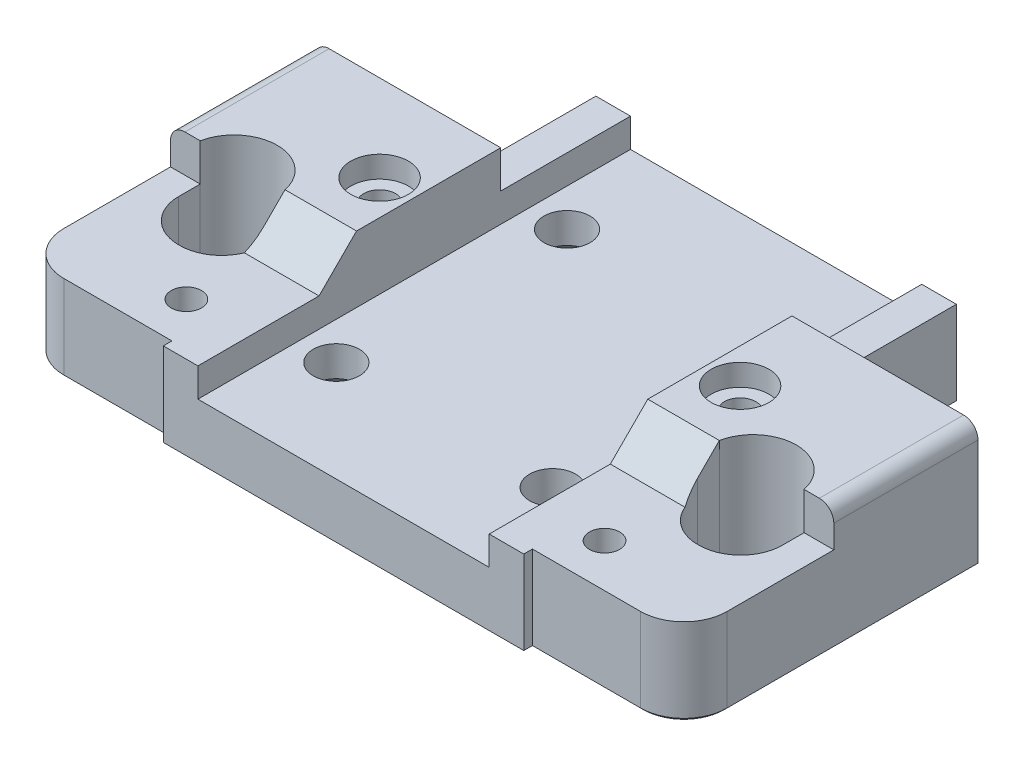
SolidWorks part; units mm, degrees
ref_plane "前视基准面" through (0, 0, 0) normal (0, 0, 1) x (1, 0, 0)
ref_plane "上视基准面" through (0, 0, 0) normal (0, 1, 0) x (1, 0, 0)
ref_plane "右视基准面" through (0, 0, 0) normal (1, 0, 0) x (0, 0, -1)
other "Configuration Table"
sketch "草图1" plane through (0, 0, 0) normal (0, 1, 0) x (1, 0, 0)
  line L1 (0, 0) -> (25, 0)
  line L2 (0, 0) -> (0, 30)
  line L3 (0, 30) -> (25, 30)
  line L4 (25, 0) -> (25, 30)
  circle A0 centre (5, 23) radius 1.6
  circle A1 centre (20, 23) radius 1.6
  circle A2 centre (20, 7) radius 1.6
  circle A3 centre (5, 7) radius 1.6
  dimension "D3" = 3.2
  dimension "D1" = 25
  dimension "D2" = 30
  dimension "D6" = 5
  dimension "D7" = 7
  dimension "D4" = 2
  dimension "D5" = 2
extrude "凸台-拉伸1" add sketch "草图1" along normal blind 4
sketch "草图5" plane through (0, 4, 0) normal (0, 1, 0) x (1, 0, 0)
  line L0 (0, 0) -> (25, 0) construction
  line L1 (0, 30) -> (2.4, 30)
  line L2 (0, 30) -> (0, 0)
  line L3 (0, 0) -> (2.4, 0)
  line L4 (2.4, 30) -> (2.4, 0)
  line L6 (25, 30) -> (22.6, 30)
  line L7 (25, 30) -> (25, 0)
  line L8 (25, 0) -> (22.6, 0)
  line L9 (22.6, 30) -> (22.6, 0)
  dimension "D1" = 2.4
  dimension "D2" = 2.4
extrude "凸台-拉伸4" add sketch "草图5" along normal blind 2
sketch "草图3" plane through (0, 0, 0) normal (0, -1, 0) x (-1, 0, 0)
  line L0 (0, 30) -> (0, 0) construction
  line L1 (0, 21) -> (10.5, 21)
  line L2 (0, 21) -> (0, 11)
  line L3 (0, 11) -> (10.5, 11)
  line L4 (10.5, 21) -> (10.5, 11)
  circle A0 centre (-5, 23) radius 1.6 construction
  dimension "D1" = 2
  dimension "D2" = 10.5
  dimension "D3" = 10
extrude "凸台-拉伸3" add sketch "草图3" against normal blind 8.6
sketch "草图4" plane through (0, 0, -21) normal (0, 0, -1) x (-1, 0, 0)
  line L1 (10.5, 8.6) -> (10.5, 0) construction
  line L2 (10.5, 8.6) -> (0, 8.6) construction
  circle A0 centre (5.5, 4.8) radius 3.15
  dimension "D1" = 6.3
  dimension "D2" = 3.8
  dimension "D3" = 5
extrude "切除-拉伸1" cut sketch "草图4" against normal blind 2.8
sketch "草图6" plane through (0, 0, 0) normal (0, -1, 0) x (-1, 0, 0)
  line L0 (0, 11) -> (10.5, 11) construction
  line L1 (10.5, 11) -> (10.5, 21) construction
  circle A0 centre (5.5, 10.4) radius 3
  dimension "D3" = 6
  dimension "D1" = 0.6
  dimension "D2" = 5
extrude "切除-拉伸2" cut sketch "草图6" against normal through all
ref_plane "基准面1" through (12.5, 0, 0) normal (1, 0, 0) x (0, 0, -1)
mirror "镜向1" about plane through (12.5, 0, 0) normal (1, 0, 0) of "凸台-拉伸3", "切除-拉伸1", "切除-拉伸2"
sketch "草图11" plane through (0, 0, 0) normal (0, -1, 0) x (-1, 0, 0)
  line L0 (-25, 30) -> (0, 30) construction
  line L2 (-23.1525, 15) -> (-24.0762, 16.6)
  line L3 (-24.0762, 16.6) -> (-25.9238, 16.6)
  line L4 (-25.9238, 16.6) -> (-26.8475, 15)
  line L5 (-26.8475, 15) -> (-25.9238, 13.4)
  line L6 (-25.9238, 13.4) -> (-24.0762, 13.4)
  line L7 (-24.0762, 13.4) -> (-23.1525, 15)
  line L8 (0.9238, 13.4) -> (1.8475, 15)
  line L9 (1.8475, 15) -> (0.9238, 16.6)
  line L10 (0.9238, 16.6) -> (-0.9238, 16.6)
  line L11 (-0.9238, 16.6) -> (-1.8475, 15)
  line L12 (-1.8475, 15) -> (-0.9238, 13.4)
  line L13 (-0.9238, 13.4) -> (0.9238, 13.4)
  circle A2 centre (-25, 15) radius 1.6 construction
  circle A3 centre (0, 15) radius 1.6 construction
  point P1 (-12.5, 30)
  dimension "D1" = 12.5
  dimension "D2" = 12.5
  dimension "D3" = 15
  dimension "D4" = 15
  dimension "D5" = 3.2
  dimension "D6" = 3.2
extrude "切除-拉伸3" cut sketch "草图11" against normal blind 4
sketch "草图18" plane through (0, 6, 0) normal (0, 1, 0) x (1, 0, 0)
  line L0 (22.6, 30) -> (22.6, 0) construction
  line L1 (25, 21) -> (22.6, 21)
  line L2 (25, 21) -> (25, 11)
  line L3 (25, 11) -> (22.6, 11)
  line L4 (22.6, 21) -> (22.6, 11)
  line L5 (2.4, 0) -> (2.4, 30) construction
  line L6 (0, 21) -> (2.4, 21)
  line L7 (0, 21) -> (0, 11)
  line L8 (0, 11) -> (2.4, 11)
  line L9 (2.4, 21) -> (2.4, 11)
extrude "凸台-拉伸8" add sketch "草图18" along normal up to surface (2.6 mm away) up to face at (-5.3333, 8.6, -14.7333)
sketch "草图12" plane through (0, 4, 0) normal (0, -1, 0) x (-1, 0, 0)
  circle A0 centre (0, 15) radius 1.1
  circle A1 centre (-25, 15) radius 1.1
  dimension "D1" = 2.2
  dimension "D2" = 2.2
extrude "切除-拉伸4" cut sketch "草图12" against normal through all
sketch "草图13" plane through (0, 8.6, 0) normal (0, 1, 0) x (1, 0, 0)
  circle A0 centre (0, 15) radius 2
  circle A1 centre (25, 15) radius 2
  dimension "D1" = 4
  dimension "D2" = 4
extrude "切除-拉伸5" cut sketch "草图13" against normal blind 1.5
chamfer "倒角10" distance 0.6 angle 45 2 edges at (0, 4, -16.1) (25, 4, -16.1)
sketch "草图22" plane through (0, 0, 0) normal (0, -1, 0) x (-1, 0, 0)
  line L0 (0, 0) -> (-25, 0) construction
  line L1 (0, 0.6) -> (10.5, 0.6)
  line L2 (0, 0.6) -> (0, 6.6)
  line L3 (0, 6.6) -> (8.4394, 6.6)
  line L4 (10.5, 0.6) -> (10.5, 6.6)
  line L5 (-25, 0.6) -> (-35.5, 0.6)
  line L6 (-25, 0.6) -> (-25, 6.6)
  line L7 (-25, 6.6) -> (-33.4394, 6.6)
  line L8 (-35.5, 0.6) -> (-35.5, 6.6)
  line L9 (-25, 0) -> (-25, 11) construction
  line L10 (0, 11) -> (0, 0) construction
  line L12 (-33.4394, 11) -> (-35.5, 11)
  line L13 (-33.4394, 11) -> (-33.4394, 6.6)
  line L15 (-35.5, 11) -> (-35.5, 6.6)
  line L16 (8.4394, 11) -> (10.5, 11)
  line L17 (8.4394, 11) -> (8.4394, 6.6)
  line L19 (10.5, 11) -> (10.5, 6.6)
  dimension "D1" = 6
  dimension "D2" = 6
  dimension "D3" = 10.5
  dimension "D4" = 10.5
  dimension "D5" = 0.6
  dimension "D6" = 0.6
  dimension "D7" = 0
  dimension "D8" = 0
extrude "凸台-拉伸10" add sketch "草图22" against normal up to surface (6 mm away) up to face at (23.8, 6, -25.5)
sketch "草图23" plane through (0, 0, 0) normal (0, -1, 0) x (-1, 0, 0)
  line L1 (2.5606, 11) -> (0, 11)
  line L2 (2.5606, 11) -> (2.5606, 6.6)
  line L3 (2.5606, 6.6) -> (0, 6.6)
  line L4 (0, 11) -> (0, 6.6)
  line L5 (-27.5606, 11) -> (-25, 11)
  line L6 (-27.5606, 11) -> (-27.5606, 6.6)
  line L7 (-27.5606, 6.6) -> (-25, 6.6)
  line L8 (-25, 11) -> (-25, 6.6)
extrude "凸台-拉伸11" add sketch "草图23" against normal up to surface (6 mm away) up to face at (-3.3079, 6, -5.84)
fillet "圆角3" radius 2.9 4 edges at (-2.5606, 3, -6.6) (-8.4394, 3, -6.6) (27.5606, 3, -6.6) (33.4394, 3, -6.6)
chamfer "倒角4" distance 2.6 angle 45 6 edges at (22.6, 7.3, -11) (25.0803, 6, -11) (2.4, 7.3, -11) (-0.0803, 6, -11) (27.5606, 6, -10.25) (-2.5606, 6, -10.25)
fillet "圆角2" radius 1 2 edges at (-10.5, 8.6, -16) (35.5, 8.6, -16)
sketch "草图19" plane through (0, 0, 0) normal (0, -1, 0) x (-1, 0, 0)
  circle A0 centre (-12.5, 11) radius 4.25
  circle A3 centre (0, 15) radius 1.1 construction
  circle A4 centre (-25, 15) radius 1.1 construction
  dimension "D1" = 8.5
  dimension "D2" = 12.5
  dimension "D3" = 4
extrude "切除-拉伸10" cut sketch "草图19" against normal blind 2.1
sketch "草图14" plane through (0, 0, 0) normal (0, -1, 0) x (1, 0, 0)
  circle A0 centre (5, -7) radius 3
  circle A1 centre (20, -7) radius 3
  circle A2 centre (20, -23) radius 3
  circle A3 centre (5, -23) radius 3
  dimension "D1" = 6
  dimension "D2" = 6
  dimension "D3" = 6
  dimension "D4" = 6
extrude "切除-拉伸6" cut sketch "草图14" against normal blind 2.5
chamfer "倒角11" distance 2 angle 45 4 edges at (20, 2.5, -26) (5, 2.5, -26) (20, 2.5, -10) (5, 2.5, -10)
sketch "草图25" plane through (0, 0, 0) normal (0, -1, 0) x (-1, 0, 0)
  line L1 (-28.8475, 3.6) -> (-27.9238, 2)
  line L2 (-27.9238, 2) -> (-26.0762, 2)
  line L3 (-26.0762, 2) -> (-25.1525, 3.6)
  line L4 (-25.1525, 3.6) -> (-26.0762, 5.2)
  line L5 (-26.0762, 5.2) -> (-27.9238, 5.2)
  line L6 (-27.9238, 5.2) -> (-28.8475, 3.6)
  line L7 (0.1525, 3.6) -> (1.0762, 2)
  line L8 (1.0762, 2) -> (2.9238, 2)
  line L9 (2.9238, 2) -> (3.8475, 3.6)
  line L10 (3.8475, 3.6) -> (2.9238, 5.2)
  line L11 (2.9238, 5.2) -> (1.0762, 5.2)
  line L12 (1.0762, 5.2) -> (0.1525, 3.6)
  line L16 (-35.5, 0.6) -> (-35.5, 21) construction
  line L18 (-35.5, 0.6) -> (-25, 0.6) construction
  line L19 (0, 0.6) -> (10.5, 0.6) construction
  line L20 (10.5, 0.6) -> (10.5, 21) construction
  circle A0 centre (-27, 3.6) radius 1.6 construction
  circle A1 centre (2, 3.6) radius 1.6 construction
  dimension "D1" = 3.2
  dimension "D2" = 3.2
  dimension "D4" = 8.5
  dimension "D6" = 3
  dimension "D3" = 3
  dimension "D5" = 8.5
extrude "切除-拉伸13" cut sketch "草图25" against normal blind 3.4
sketch "草图26" plane through (0, 3.4, 0) normal (0, -1, 0) x (-1, 0, 0)
  line L0 (-27.9238, 2) -> (-26.0762, 2) construction
  line L1 (1.0762, 2) -> (2.9238, 2) construction
  circle A0 centre (2, 3.6) radius 1.05
  circle A1 centre (-27, 3.6) radius 1.05
  point P9 (-27, 2)
  point P12 (2, 2)
  dimension "D1" = 2.1
  dimension "D2" = 2.1
  dimension "D5" = 0
  dimension "D3" = 0
  dimension "D4" = 0
  dimension "D6" = 0
extrude "切除-拉伸14" cut sketch "草图26" against normal blind 3
chamfer "倒角12" distance 0.6 angle 45 2 edges at (-2, 3.4, -4.65) (27, 3.4, -4.65)
chamfer "倒角13" distance 0.2 angle 45 12 edges at (27, 0, -2) (25.6144, 0, -2.8) (25.6144, 0, -4.4) (27, 0, -5.2) (28.3856, 0, -4.4) (28.3856, 0, -2.8) (-3.3856, 0, -2.8) (-3.3856, 0, -4.4) (-2, 0, -5.2) (-0.6144, 0, -4.4) (-0.6144, 0, -2.8) (-2, 0, -2)
fillet "圆角4" radius 3 2 edges at (35.5, 3, -0.6) (-10.5, 3, -0.6)
chamfer "倒角14" distance 0.2 angle 45 27 edges at (30.5, 0, -13.4) (0, 0, -0.3) (-3.75, 0, -0.6) (-8.4394, 0, -10.25) (27.5606, 0, -10.25) (-5.5, 0, -6.6) (-2.5606, 0, -10.25) (30.5, 0, -6.6) (33.4394, 0, -10.25) (-3.41, 0, -7.4494) (-7.59, 0, -7.4494) (28.41, 0, -7.4494) (32.59, 0, -7.4494) (12.5, 0, -15.25) (12.5, 0, -30) (25, 0, -0.3) (35.5, 0, -12.3) (-10.5, 0, -12.3) (28.75, 0, -0.6) (-9.6213, 0, -1.4787) (34.6213, 0, -1.4787) (12.5, 0, 0) (-5.25, 0, -21) (0, 0, -25.5) (-5.5, 0, -13.4) (25, 0, -25.5) (30.25, 0, -21)
equation "\"D6@草图1\"=\"D1@草图1\"/2-15/2"
equation "\"D7@草图1\"=\"D2@草图1\"/2-16/2"
equation "\"D1@草图5\"=\"D1@草图1\"/2-20.2/2"
equation "\"D2@草图5\"=\"D1@草图5\""
